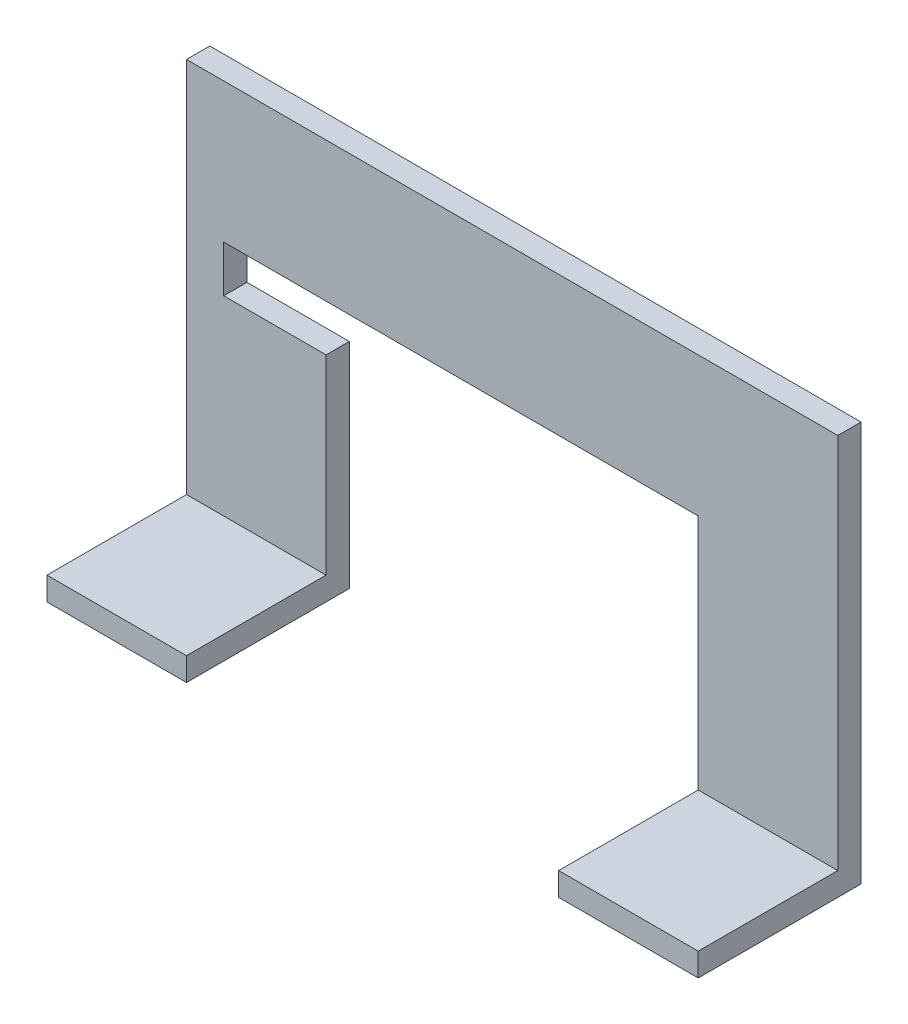
SolidWorks part; units mm, degrees
ref_plane "Front Plane" through (0, 0, 0) normal (0, 0, 1) x (1, 0, 0)
ref_plane "Top Plane" through (0, 0, 0) normal (0, 1, 0) x (1, 0, 0)
ref_plane "Right Plane" through (0, 0, 0) normal (1, 0, 0) x (0, 0, -1)
sketch "Sketch1" plane through (0, 0, 0) normal (0, 0, 1) x (1, 0, 0)
  line L0 (-35, 0) -> (35, 0)
  line L1 (35, 0) -> (35, -43)
  line L2 (35, -43) -> (20, -43)
  line L3 (20, -43) -> (20, -15)
  line L4 (20, -15) -> (-31, -15)
  line L5 (-31, -15) -> (-31, -20)
  line L6 (-31, -20) -> (-20, -20)
  line L7 (-20, -20) -> (-20, -43)
  line L8 (-20, -43) -> (-35, -43)
  line L9 (-35, -43) -> (-35, 0)
  point P4 (0, 0)
  dimension "D1" = 70
  dimension "D2" = 43
  dimension "D3" = 5
  dimension "D4" = 23
  dimension "D5" = 43
  dimension "D6" = 4
  dimension "D7" = 15
  dimension "D8" = 15
base flange "Base-Flange1" sketch "Sketch1" thickness 2.5 reverse thickness direction no parameters "D1"=1
sketch "Sketch6" plane through (0, 0, 0) normal (0, 0, 1) x (1, 0, 0)
  line L0 (-35, 0) -> (-35, -43) construction
  line L1 (-35, -40.5) -> (-20, -40.5)
  line L2 (-35, -40.5) -> (-35, -43)
  line L3 (-35, -43) -> (-20, -43)
  line L4 (-20, -40.5) -> (-20, -43)
  dimension "D1" = 2.5
extrude "Boss-Extrude1" add sketch "Sketch6" along normal blind 15
mirror "Mirror1" about plane through (0, 0, 0) normal (1, 0, 0) of "Boss-Extrude1"
sketch "Bend-Lines1" [suppressed] plane through (0, 0, 0) normal (0, 1, 0) x (1, 0, 0)
sketch "Bounding-Box1" [suppressed] plane through (0, 0, 0) normal (0, 1, 0) x (1, 0, 0)
sheet metal parameters "Sheet-Metal1" thickness 2.5 parameters "D1"=1
flat pattern "Flat-Pattern1" [suppressed]
sketch "Bend-Lines2" plane through (0, 0, 0) normal (0, 1, 0) x (1, 0, 0)
sketch3d "Bounding-Box2" [suppressed]
  line L0 (35, -43, 0) -> (-35, -43, 0) construction
  line L1 (35, 0, 0) -> (-35, 0, 0) construction
  line L2 (35, -43, 0) -> (35, 0, 0) construction
  line L3 (-35, -43, 0) -> (-35, 0, 0) construction
sheet metal parameters "Sheet-Metal2" thickness 2.5 parameters "D1"=1
flat pattern "Flat-Pattern1"
sketch "Bend-Lines2" plane through (0, 0, 0) normal (0, 1, 0) x (1, 0, 0)
sketch3d "Bounding-Box2" [suppressed]
  line L0 (-35, -43, 0) -> (35, -43, 0) construction
  line L1 (-35, 0, 0) -> (35, 0, 0) construction
  line L2 (-35, -43, 0) -> (-35, 0, 0) construction
  line L3 (35, -43, 0) -> (35, 0, 0) construction
sheet metal parameters "Sheet-Metal3" thickness 2.5 parameters "D1"=1
flat pattern "Flat-Pattern1"
sketch "Bend-Lines2" plane through (0, 0, 0) normal (0, 1, 0) x (1, 0, 0)
sketch3d "Bounding-Box2" [suppressed]
  line L0 (-35, -40.5, 0) -> (35, -40.5, 0) construction
  line L1 (-35, 0, 0) -> (35, 0, 0) construction
  line L2 (-35, -40.5, 0) -> (-35, 0, 0) construction
  line L3 (35, -40.5, 0) -> (35, 0, 0) construction
